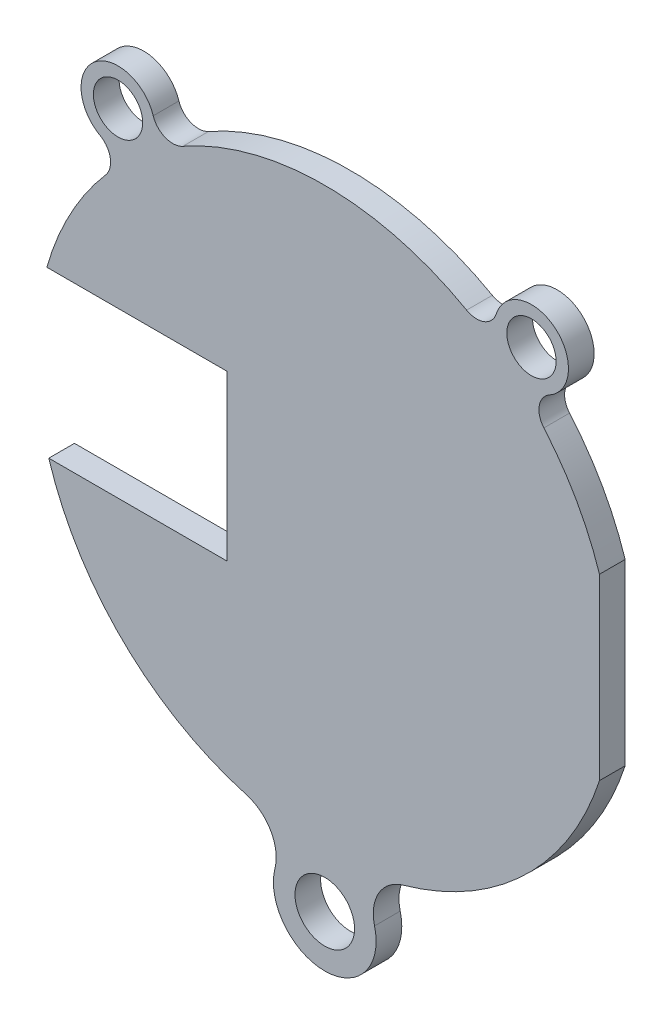
SolidWorks part; units mm, degrees
ref_plane "Front Plane" through (0, 0, 0) normal (0, 0, 1) x (1, 0, 0)
ref_plane "Top Plane" through (0, 0, 0) normal (0, 1, 0) x (1, 0, 0)
ref_plane "Right Plane" through (0, 0, 0) normal (1, 0, 0) x (0, 0, -1)
sketch "Sketch1" plane through (0, 0, 0) normal (0, 0, 1) x (1, 0, 0)
  line L0 (-6.0563, 4.8768) -> (-17.1812, 4.8768) construction
  line L2 (-17.0607, -5.2832) -> (-6.0563, -5.2832) construction
  line L5 (16.9841, -5.5245) -> (16.9841, 5.5245) construction
  line L10 (-6.0563, 4.8768) -> (-17.1812, 4.8768)
  line L11 (-6.0563, 4.8768) -> (-6.0563, -5.2832)
  line L12 (-17.0607, -5.2832) -> (-6.0563, -5.2832)
  line L15 (16.9841, -5.5245) -> (16.9841, 5.5245)
  arc A0 (-17.0607, -5.2832) -> (-4.8506, -17.1887) centre (0, 0) ccw construction
  arc A3 (4.8506, -17.1887) -> (16.9841, -5.5245) centre (0, 0) ccw construction
  arc A4 (16.9841, 5.5245) -> (13.5462, 11.6395) centre (0, 0) ccw construction
  arc A8 (-13.5462, 11.6395) -> (-17.1812, 4.8768) centre (0, 0) ccw construction
  arc A9 (-17.0607, -5.2832) -> (-4.8506, -17.1887) centre (0, 0) ccw
  arc A10 (4.8506, -17.1887) -> (3.078, -20.2562) centre (5.5404, -19.6332) ccw construction
  arc A11 (-3.078, -20.2562) -> (3.078, -20.2562) centre (0, -21.035) ccw construction
  arc A12 (4.8506, -17.1887) -> (16.9841, -5.5245) centre (0, 0) ccw
  arc A13 (16.9841, 5.5245) -> (13.5462, 11.6395) centre (0, 0) ccw
  arc A14 (-3.078, -20.2562) -> (-4.8506, -17.1887) centre (-5.5404, -19.6332) ccw construction
  arc A15 (8.7709, 15.5579) -> (-8.7709, 15.5579) centre (0, 0) ccw
  arc A16 (-13.5462, 11.6395) -> (-13.8916, 13.5768) centre (-14.5094, 12.4672) ccw construction
  arc A17 (-13.5462, 11.6395) -> (-17.1812, 4.8768) centre (0, 0) ccw
  arc A20 (-10.6034, 16.2749) -> (-13.8916, 13.5768) centre (-12.7793, 15.574) ccw construction
  arc A21 (-10.6034, 16.2749) -> (-8.7709, 15.5579) centre (-9.3946, 16.6642) ccw construction
  arc A22 (8.7709, 15.5579) -> (10.6034, 16.2749) centre (9.3946, 16.6642) ccw construction
  arc A23 (13.8916, 13.5768) -> (10.6034, 16.2749) centre (12.7793, 15.574) ccw construction
  arc A24 (13.8916, 13.5768) -> (13.5462, 11.6395) centre (14.5094, 12.4672) ccw construction
  arc A25 (4.8506, -17.1887) -> (3.078, -20.2562) centre (5.5404, -19.6332) ccw
  arc A26 (-3.078, -20.2562) -> (3.078, -20.2562) centre (0, -21.035) ccw
  arc A27 (-3.078, -20.2562) -> (-4.8506, -17.1887) centre (-5.5404, -19.6332) ccw
  arc A28 (-13.5462, 11.6395) -> (-13.8916, 13.5768) centre (-14.5094, 12.4672) ccw
  arc A29 (-10.6034, 16.2749) -> (-13.8916, 13.5768) centre (-12.7793, 15.574) ccw
  arc A30 (-10.6034, 16.2749) -> (-8.7709, 15.5579) centre (-9.3946, 16.6642) ccw
  arc A31 (8.7709, 15.5579) -> (10.6034, 16.2749) centre (9.3946, 16.6642) ccw
  arc A32 (13.8916, 13.5768) -> (10.6034, 16.2749) centre (12.7793, 15.574) ccw
  arc A33 (13.8916, 13.5768) -> (13.5462, 11.6395) centre (14.5094, 12.4672) ccw
  circle A34 centre (0, -21.035) radius 1.8415 construction
  circle A35 centre (12.7793, 15.574) radius 1.524 construction
  circle A36 centre (-12.7793, 15.574) radius 1.524 construction
  circle A37 centre (0, -21.035) radius 1.8415
  circle A38 centre (12.7793, 15.574) radius 1.524
  circle A39 centre (-12.7793, 15.574) radius 1.524
extrude "Boss-Extrude1" add sketch "Sketch1" along normal blind 1.5875
